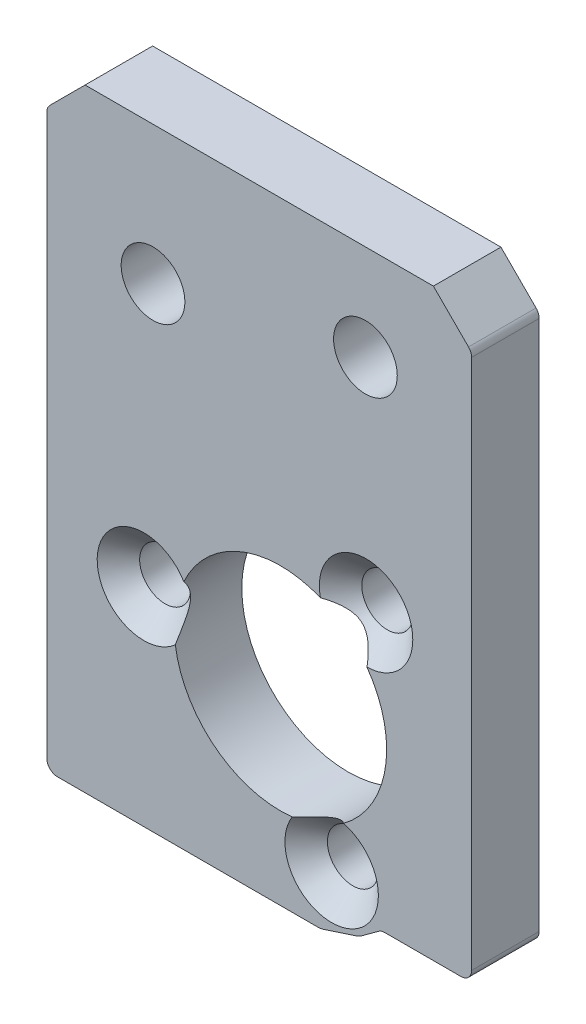
SolidWorks part; units mm, degrees
ref_plane "Front Plane" through (0, 0, 0) normal (0, 0, 1) x (1, 0, 0)
ref_plane "Top Plane" through (0, 0, 0) normal (0, 1, 0) x (1, 0, 0)
ref_plane "Right Plane" through (0, 0, 0) normal (1, 0, 0) x (0, 0, -1)
sketch "Sketch1" plane through (0, 0, 0) normal (0, 0, 1) x (1, 0, 0)
  line L1 (0, 0) -> (20, 0)
  line L2 (0, 0) -> (0, 29.11)
  line L3 (0, 29.11) -> (20, 29.11)
  line L4 (20, 0) -> (20, 29.11)
  circle A0 centre (5, 22.61) radius 1.5
  circle A1 centre (15, 24.61) radius 1.5
  arc A2 (15.0728, 12.0104) -> (12.8801, 13.743) centre (15.03, 14.21) ccw
  arc A3 (6.4499, 11.1828) -> (6.049, 8.4114) centre (4.57, 10.04) ccw
  arc A4 (11.5537, 4.1408) -> (13.9699, 5.0876) centre (13.41, 2.96) ccw
  circle A7 centre (15.03, 14.21) radius 1.2
  circle A8 centre (4.57, 10.04) radius 1.2
  circle A9 centre (13.41, 2.96) radius 1.2
  circle A10 centre (11, 9.11) radius 5
extrude "Boss-Extrude2" add sketch "Sketch1" against normal blind 3.18 contours A0 | A1 | L2 L1 L4 L3 | A7 | A10 | A8 | A9 region at (5, 22.61, 0) region at (15, 24.61, 0)
hole_wizard "CSK for M2 Flat Head Machine Screw1" positions "Sketch10" profile "Sketch11" countersink size "M2" standard "ANSI Metric"
sketch "Sketch10" plane through (0, 0, 0) normal (0, 0, 1) x (1, 0, 0)
  point P0 (4.57, 10.04)
  point P3 (15.03, 14.21)
  point P6 (13.41, 2.96)
sketch "Sketch11" plane through (4.57, 10.04, 0) normal (1, 0, 0) x (0, -1, 0)
  line L0 (0, 0) -> (0, 4.23)
  line L1 (0, 4.23) -> (1.2, 3.509)
  line L2 (1.2, 3.509) -> (1.2, 1)
  line L3 (1.2, 1) -> (2.2, 0)
  line L5 (2.2, 0) -> (0, 0)
  line L6 (-1.2, 1) -> (-2.2, 0) construction
  line L10 (0, 4.23) -> (-1.2, 3.509) construction
  line L11 (0, -6.35) -> (0, 107.95) construction
  dimension "Hole Dia." = 2.4
  dimension "Hole Depth" = 4.23
  dimension "Near C'Sink Dia." = 4.4
  dimension "Near C'Sink Angle" = 90
  dimension "Drill Angle" = 118
chamfer "Chamfer1" distance 1.8 angle 45 2 edges at (0, 29.11, -1.59) (20, 29.11, -1.59)
fillet "Fillet1" radius 0.5 2 edges at (20, 27.31, -1.59) (0, 27.31, -1.59)
sketch "Sketch12" plane through (0, 0, -3.18) normal (0, 0, -1) x (-1, 0, 0)
  line L0 (0, 0) -> (-20, 0)
  line L1 (0, 0) -> (-20, 0) construction
  line L2 (-20, 0) -> (-20, 1.6068)
  line L3 (-20, 0) -> (-20, 27.1029) construction
  line L4 (-20, 1.6068) -> (-15.7486, 1.6068)
  line L6 (0, 0) -> (-20, 0) construction
  line L8 (0, 0.2514) -> (-13.8989, 0.2514)
  line L9 (-13.8989, 0.2514) -> (-15.7486, 1.6068)
  line L10 (0, 0) -> (0, 27.1029) construction
  line L11 (0, 0.2514) -> (0, 0)
extrude "Cut-Extrude1" cut sketch "Sketch12" against normal blind 4
fillet "Fillet6" radius 0.5 3 edges at (0, 0.2514, -1.59) (15.7486, 1.6068, -1.59) (20, 1.6068, -1.59)
sketch "Sketch14" plane through (0, 0, 0) normal (0, 0, 1) x (1, 0, 0)
  line L0 (12.8989, 0.2514) -> (13.8989, 0.2514)
  line L1 (13.8989, 0.2514) -> (0.5, 0.2514) construction
  line L2 (13.8989, 0.2514) -> (14.7055, 0.8424)
  line L3 (15.6166, 1.5101) -> (13.8989, 0.2514) construction
  line L4 (14.7055, 0.8424) -> (12.8989, 0.2514)
extrude "Cut-Extrude2" cut sketch "Sketch14" against normal blind 4
fillet "Fillet8" radius 1 2 edges at (12.8989, 0.2514, -1.59) (14.7055, 0.8424, -1.59)
